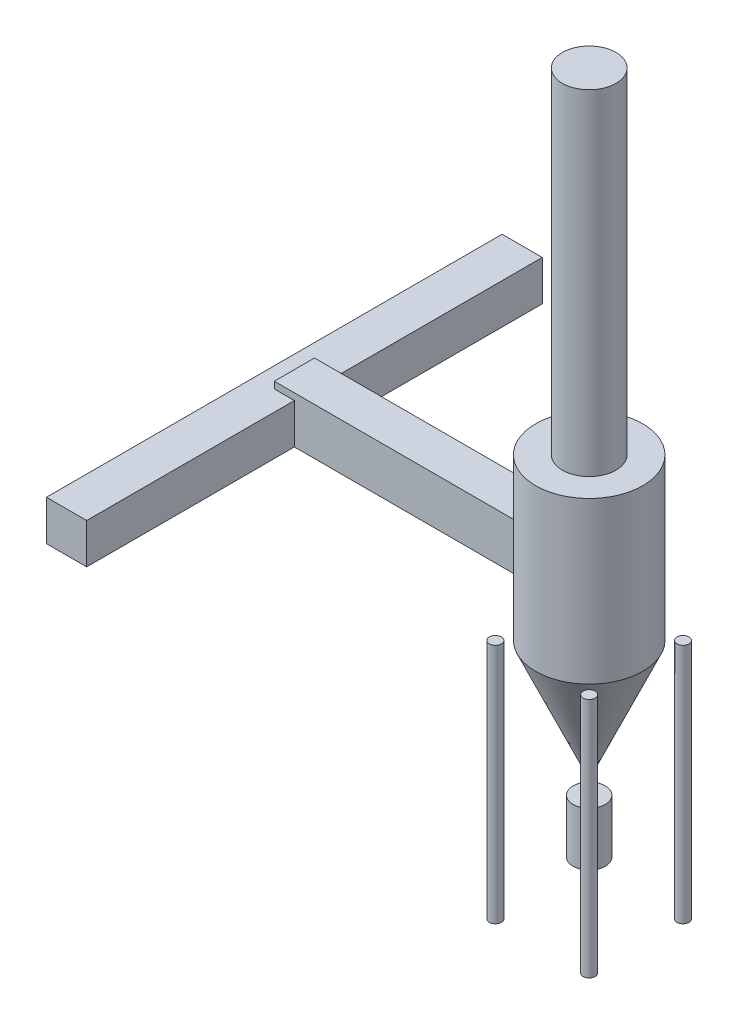
SolidWorks part; units mm, degrees
ref_plane "Front Plane" through (0, 0, 0) normal (0, 0, 1) x (1, 0, 0)
ref_plane "Top Plane" through (0, 0, 0) normal (0, 1, 0) x (1, 0, 0)
ref_plane "Right Plane" through (0, 0, 0) normal (1, 0, 0) x (0, 0, -1)
other "Configuration Table"
sketch "Sketch1" plane through (0, 0, 0) normal (0, 1, 0) x (1, 0, 0)
  circle A0 centre (1850, 5150) radius 45
extrude "Boss-Extrude1" add sketch "Sketch1" along normal blind 1800
sketch "Sketch2" plane through (0, 0, 0) normal (0, 1, 0) x (1, 0, 0)
  circle A0 centre (2550, 5150) radius 45
extrude "Boss-Extrude2" add sketch "Sketch2" along normal blind 1800
sketch "Sketch3" plane through (0, 0, 0) normal (0, 1, 0) x (1, 0, 0)
  circle A0 centre (1850, 5850) radius 45
extrude "Boss-Extrude3" add sketch "Sketch3" along normal blind 1800
sketch "Sketch4" plane through (0, 0, 0) normal (0, 1, 0) x (1, 0, 0)
  circle A0 centre (2550, 5850) radius 45
extrude "Boss-Extrude4" add sketch "Sketch4" along normal blind 1800
sketch "Sketch5" plane through (0, 0, 0) normal (0, 1, 0) x (1, 0, 0)
  circle A0 centre (2200, 5500) radius 120
extrude "Boss-Extrude5" add sketch "Sketch5" along normal blind 400 from offset 400
sketch "Sketch6" plane through (0, 0, 0) normal (0, 1, 0) x (1, 0, 0)
  circle A0 centre (2200, 5500) radius 400
extrude "Boss-Extrude6" add sketch "Sketch6" against normal blind 1000 draft 24 from offset 1800 flip side to cut
sketch "Sketch7" plane through (0, 0, 0) normal (0, 1, 0) x (1, 0, 0)
  circle A0 centre (2200, 5500) radius 400
extrude "Boss-Extrude7" add sketch "Sketch7" along normal blind 1200 from offset 1800
sketch "Sketch8" plane through (0, 0, 0) normal (0, 1, 0) x (1, 0, 0)
  circle A0 centre (2200, 5500) radius 200
extrude "Boss-Extrude8" add sketch "Sketch8" along normal blind 2500 from offset 3000
sketch "Sketch9" plane through (0, 0, 0) normal (0, 1, 0) x (1, 0, 0)
  line L1 (-150, 3800) -> (150, 3800)
  line L2 (-150, 3800) -> (-150, 7200)
  line L3 (-150, 7200) -> (150, 7200)
  line L4 (150, 3800) -> (150, 7200)
extrude "Boss-Extrude9" add sketch "Sketch9" along normal blind 300 from offset 2100
sketch "Sketch10" plane through (0, 0, 0) normal (0, 1, 0) x (1, 0, 0)
  line L1 (0, 5350) -> (1800, 5350)
  line L2 (0, 5350) -> (0, 5650)
  line L3 (0, 5650) -> (1800, 5650)
  line L4 (1800, 5350) -> (1800, 5650)
extrude "Boss-Extrude10" add sketch "Sketch10" along normal blind 350 from offset 2100
